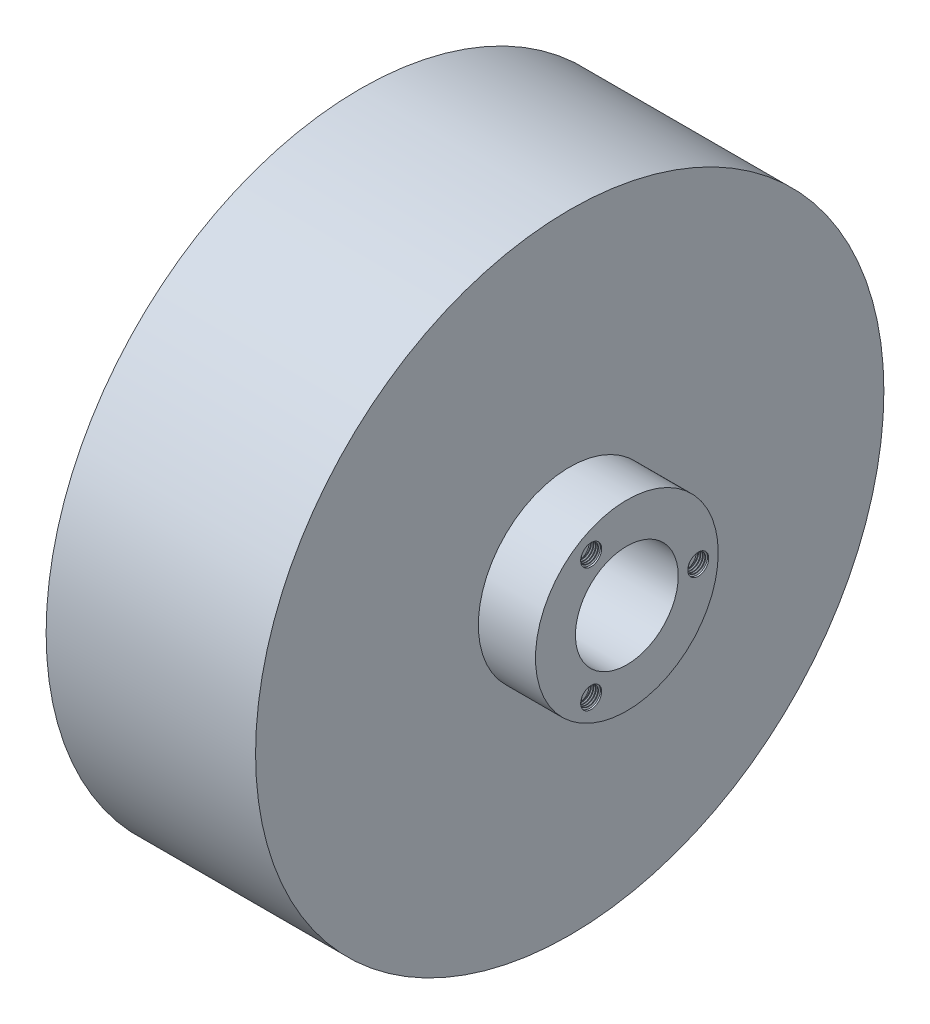
SolidWorks part; units mm, degrees
material "AISI 304"
ref_plane "Front Plane" through (0, 0, 0) normal (0, 0, 1) x (1, 0, 0)
ref_plane "Top Plane" through (0, 0, 0) normal (0, 1, 0) x (1, 0, 0)
ref_plane "Right Plane" through (0, 0, 0) normal (1, 0, 0) x (0, 0, -1)
sketch "Sketch1" plane through (0, 0, 0) normal (1, 0, 0) x (0, 0, -1)
  circle A0 centre (0, 0) radius 165
extrude "Boss-Extrude1" add sketch "Sketch1" along normal blind 110 contours A0
sketch "Sketch2" plane through (110, 0, 0) normal (1, 0, 0) x (0, 0, -1)
  circle A0 centre (0, 0) radius 48
extrude "Boss-Extrude2" add sketch "Sketch2" along normal blind 30 contours A0
sketch "Sketch3" plane through (140, 0, 0) normal (1, 0, 0) x (0, 0, -1)
  circle A0 centre (0, 0) radius 27
extrude "Cut-Extrude1" cut sketch "Sketch3" against normal blind 40 contours A0
sketch "Sketch12" plane through (140, 0, 0) normal (1, 0, 0) x (0, 0, -1)
  circle A2 centre (37.5, 0) radius 5.5
extrude "Cut-Extrude2" cut sketch "Sketch12" against normal blind 6 contours A2
pattern_circular "CirPattern1" count 3 over 360 about axis through (100, 0, 0) along (1, 0, 0) of "Cut-Extrude2"
thread "Thread1" pitch 1.25 method extrude profile "Thread Profile2" start angle 0, offset 0, length 0, pitch 1.25, diameter 11
ref_plane "Plane2" through (140, 0, -32) normal (0, -1, 0) x (0, 0, 1)
sketch "Thread Profile2" plane through (140, 0, -32) normal (0, -1, 0) x (0, 0, 1)
  line L0 (0, 0) -> (0, 1.25) construction
  line L11 (0, 0) -> (0, 1.0937)
  line L12 (0, 1.0937) -> (-0.6766, 0.7031)
  line L13 (-0.6766, 0.7031) -> (-0.6766, 0.3906)
  line L15 (-0.6766, 0.3906) -> (0, 0)
  line L17 (-0.6766, 0.5469) -> (0, 0.5469) construction
  point P2 (0, 0)
  dimension "Pitch" = 1.25
  dimension "Profile_Angle" = 60
  dimension "Profile_Land" = 0.3125
  dimension "Profile_Height" = 0.6766
thread "Thread2" pitch 1.25 method extrude profile "Thread Profile3" start angle 0, offset 0, length 0, pitch 1.25, diameter 11
ref_plane "Plane3" through (140, 32.476, 24.25) normal (0, -1, 0) x (0, 0, 1)
sketch "Thread Profile3" plane through (140, 32.476, 24.25) normal (0, -1, 0) x (0, 0, 1)
  line L0 (0, 0) -> (0, 1.25) construction
  line L11 (0, 0) -> (0, 1.0937)
  line L12 (0, 1.0937) -> (-0.6766, 0.7031)
  line L13 (-0.6766, 0.7031) -> (-0.6766, 0.3906)
  line L15 (-0.6766, 0.3906) -> (0, 0)
  line L17 (-0.6766, 0.5469) -> (0, 0.5469) construction
  point P2 (0, 0)
  dimension "Pitch" = 1.25
  dimension "Profile_Angle" = 60
  dimension "Profile_Land" = 0.3125
  dimension "Profile_Height" = 0.6766
thread "Thread3" pitch 1.25 method extrude profile "Thread Profile4" start angle 0, offset 0, length 0, pitch 1.25, diameter 11
ref_plane "Plane4" through (140, -32.476, 24.25) normal (0, -1, 0) x (0, 0, 1)
sketch "Thread Profile4" plane through (140, -32.476, 24.25) normal (0, -1, 0) x (0, 0, 1)
  line L0 (0, 0) -> (0, 1.25) construction
  line L11 (0, 0) -> (0, 1.0937)
  line L12 (0, 1.0937) -> (-0.6766, 0.7031)
  line L13 (-0.6766, 0.7031) -> (-0.6766, 0.3906)
  line L15 (-0.6766, 0.3906) -> (0, 0)
  line L17 (-0.6766, 0.5469) -> (0, 0.5469) construction
  point P2 (0, 0)
  dimension "Pitch" = 1.25
  dimension "Profile_Angle" = 60
  dimension "Profile_Land" = 0.3125
  dimension "Profile_Height" = 0.6766
